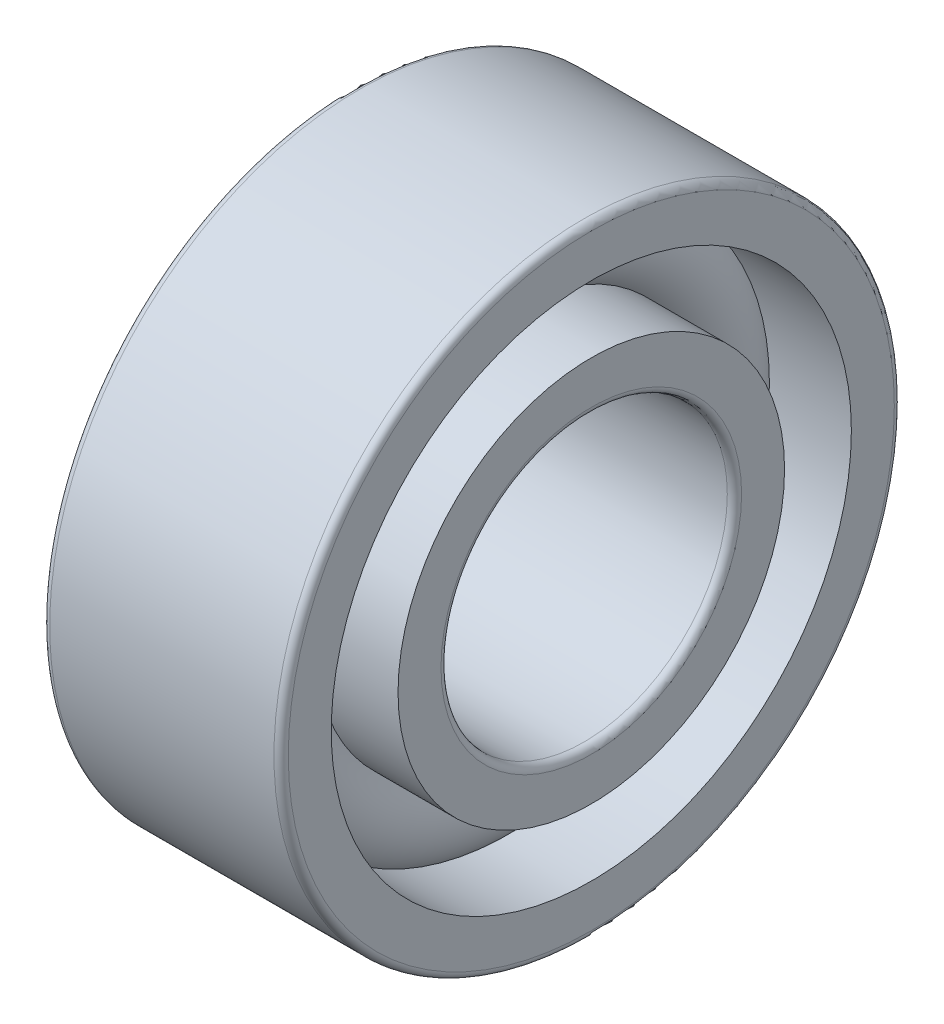
SolidWorks part; units mm, degrees
ref_plane "Plane1" through (0, 0, 0) normal (0, 0, 1) x (1, 0, 0)
ref_plane "Plane2" through (0, 0, 0) normal (0, 1, 0) x (1, 0, 0)
ref_plane "Plane3" through (0, 0, 0) normal (1, 0, 0) x (0, 0, -1)
other "Configuration Table"
sketch "Clipboard" plane through (0, 0, 0) normal (0, 0, 1) x (1, 0, 0)
  line L0 (-10, 0) -> (10, 0) construction
  line L1 (0, 0) -> (22.3471, -0.7804)
  line L2 (0, 0) -> (4.7471, 0.1658)
  line L3 (0, 0) -> (22.3471, -0.7804)
  line L4 (0, 0) -> (-22.3573, -0.3902)
  dimension "Count" = 2
sketch "CagSpiSke" plane through (0, 0, 0) normal (0, 0, 1) x (1, 0, 0)
  line L0 (0.105, 4.575) -> (0.105, 4.925)
  line L1 (0.105, 4.925) -> (-0.105, 4.925)
  line L2 (-0.105, 4.925) -> (-0.105, 4.575)
  line L3 (-0.105, 4.575) -> (0.105, 4.575)
  line L4 (-20.6375, 0) -> (20.6375, 0) construction
  line L5 (0, 0) -> (0, 23.7692) construction
revolve "CageSpine" add sketch "CagSpiSke" angle 0.001 about L4 reverse direction yes
ref_axis "Axis1" through (-50, 0, 0) along (1, 0, 0)
sketch "CagBalSke" plane through (0, 0, 0) normal (0, 0, 1) x (1, 0, 0)
  line L0 (-1.155, 4.75) -> (1.155, 4.75)
  line L1 (-1.905, 4.75) -> (1.905, 4.75) construction
  line L2 (-10, 0) -> (10, 0) construction
  line L3 (0, 0) -> (0, 24) construction
  arc A0 (1.155, 4.75) -> (-1.155, 4.75) centre (0, 4.75) cw
revolve "CageBall" [suppressed] add sketch "CagBalSke" angle 360 about L1 reverse direction yes
pattern_circular "CageBalls" [suppressed] count 2 every 180 about axis through (-50, 0, 0) along (1, 0, 0)
sketch "CagTrmODSke" plane through (0, 0, 0) normal (0, 0, 1) x (1, 0, 0)
  line L0 (1.156, 4.925) -> (1.156, 5.906)
  line L1 (1.156, 5.906) -> (-1.156, 5.906)
  line L2 (-1.156, 5.906) -> (-1.156, 4.925)
  line L3 (-1.156, 4.925) -> (1.156, 4.925)
  line L4 (-20.6375, 0) -> (20.6375, 0) construction
  line L5 (0, 0) -> (0, 25) construction
revolve "CageTrimOD" [suppressed] cut sketch "CagTrmODSke" angle 360 about L4 reverse direction yes
sketch "CagTrmIDSke" plane through (0, 0, 0) normal (0, 0, 1) x (1, 0, 0)
  line L0 (1.156, 3.596) -> (1.156, 4.575)
  line L1 (1.156, 4.575) -> (-1.156, 4.575)
  line L2 (-1.156, 4.575) -> (-1.156, 3.596)
  line L3 (-1.156, 3.596) -> (1.156, 3.596)
  line L4 (-20.6375, 0) -> (20.6375, 0) construction
  line L5 (0, 0) -> (0, 25) construction
revolve "CageTrimID" [suppressed] cut sketch "CagTrmIDSke" angle 360 about L4 reverse direction yes
sketch "BalSimSke" plane through (0, 0, 0) normal (0, 0, 1) x (1, 0, 0)
  line L0 (-10, 0) -> (10, 0) construction
  line L1 (-10, 4.75) -> (10, 4.75) construction
  line L2 (0, 0) -> (0, 23) construction
  circle A0 centre (0, 4.75) radius 1.05
revolve "BallsSimplified" add sketch "BalSimSke" angle 360 about L0
sketch "BalDetSke" plane through (0, 0, 0) normal (0, 0, 1) x (1, 0, 0)
  line L0 (-1.05, 4.75) -> (1.05, 4.75)
  line L1 (-1.905, 4.75) -> (1.905, 4.75) construction
  line L2 (0, 0) -> (0, 25) construction
  arc A0 (1.05, 4.75) -> (-1.05, 4.75) centre (0, 4.75) cw
revolve "BallDetailed" [suppressed] add sketch "BalDetSke" angle 360 about L1 reverse direction yes
sketch "InnRacSke" plane through (0, 0, 0) normal (0, 0, 1) x (1, 0, 0)
  line L0 (-0.7487, 4.05) -> (-2.5, 4.05)
  line L1 (-2.5, 4.05) -> (-2.5, 3.15)
  line L2 (-2.35, 3) -> (2.35, 3)
  line L3 (2.5, 3.15) -> (2.5, 4.05)
  line L4 (2.5, 4.05) -> (0.7487, 4.05)
  line L5 (-20.6375, 0) -> (20.6375, 0) construction
  line L6 (0, 0) -> (0, 30) construction
  arc A0 (-2.5, 3.15) -> (-2.35, 3) centre (-2.35, 3.15) ccw
  arc A1 (2.35, 3) -> (2.5, 3.15) centre (2.35, 3.15) ccw
  arc A2 (0.7487, 4.05) -> (-0.7487, 4.05) centre (0, 4.75) cw
revolve "InnerRace" add sketch "InnRacSke" angle 360 about L5 reverse direction yes
sketch "OutRacSke" plane through (0, 0, 0) normal (0, 0, 1) x (1, 0, 0)
  line L0 (-0.7487, 5.45) -> (-2.5, 5.45)
  line L1 (-2.5, 5.45) -> (-2.5, 6.35)
  line L2 (-2.35, 6.5) -> (2.35, 6.5)
  line L3 (2.5, 6.35) -> (2.5, 5.45)
  line L4 (2.5, 5.45) -> (0.7487, 5.45)
  line L5 (-20.6375, 0) -> (20.6375, 0) construction
  line L6 (0, 0) -> (0, 30) construction
  arc A0 (-2.5, 6.35) -> (-2.35, 6.5) centre (-2.35, 6.35) cw
  arc A1 (2.35, 6.5) -> (2.5, 6.35) centre (2.35, 6.35) cw
  arc A2 (0.7487, 5.45) -> (-0.7487, 5.45) centre (0, 4.75) ccw
revolve "OuterRace" add sketch "OutRacSke" angle 360 about L5 reverse direction yes
pattern_circular "BallsDetailed" [suppressed] count 2 every 180 about axis through (-50, 0, 0) along (1, 0, 0)
equation "\"BallCLRad@Clipboard\" = ( \"OD@OutRacSke\" + \"ID@InnRacSke\" ) / 4"
equation "\"BallCLRad@BalSimSke\" = \"BallCLRad@Clipboard\""
equation "\"BallCLRad@BalDetSke\" = \"BallCLRad@Clipboard\""
equation "\"BallCLRad@InnRacSke\" = \"BallCLRad@Clipboard\""
equation "\"BallCLRad@OutRacSke\" = \"BallCLRad@Clipboard\""
equation "\"Ball_diameter@InnRacSke\" = \"Ball_diameter@BalDetSke\" - 0.05"
equation "\"Ball_diameter@OutRacSke\" = \"Ball_diameter@BalDetSke\" - 0.05"
equation "\"Ball_diameter@BalSimSke\" = \"Ball_diameter@BalDetSke\""
equation "\"Width@OutRacSke\" = \"Width@InnRacSke\""
equation "\"Fillet_radius@OutRacSke\" = \"Fillet_radius@InnRacSke\""
equation "\"Max_count@Clipboard\" = int( 3.14159265 / atn(( \"Ball_diameter@BalDetSke\" / 2) / sqr( \"BallCLRad@Clipboard\"  *  \"BallCLRad@Clipboard\" - ( \"Ball_diameter@BalDetSke\" / 2) *  ( \"Ball_diameter@BalDetSke\" / 2))))"
equation "\"Max_count@Clipboard\" = ((sgn( \"Max_count@Clipboard\" - \"Count@Clipboard\" )-1)*( \"Max_count@Clipboard\" - \"Count@Clipboard\" ))/-2+ \"Count@Clipboard\""
equation "\"Count@BallsDetailed\" = int( \"Show_count@Clipboard\" ) "
equation "\"Count@BallsDetailed\" = ((sgn( \"Count@BallsDetailed\" - \"Max_count@Clipboard\" )-1)*( \"Count@BallsDetailed\" - \"Max_count@Clipboard\" ))/-2+ \"Max_count@Clipboard\""
equation "\"Count@BallsDetailed\" = ((sgn( \"Count@BallsDetailed\" - \"Min_count@Clipboard\" )+1)*( \"Count@BallsDetailed\" - \"Min_count@Clipboard\"))/2 +\"Min_count@Clipboard\""
equation "\"Angle@BallsDetailed\" = 360.0 / \"Max_count@Clipboard\""
equation "\"BallCLRad@CagBalSke\" = \"BallCLRad@Clipboard\""
equation "\"Count@CageBalls\" = \"Count@BallsDetailed\""
equation "\"Angle@CageBalls\" = \"Angle@BallsDetailed\""
equation "\"Angle@CageSpine\" =  \"Angle@CageBalls\" * ( \"Count@CageBalls\" -1 + int( \"Count@CageBalls\" / \"Max_count@Clipboard\" ) )  + 0.001 -  int( \"Count@CageBalls\" / \"Max_count@Clipboard\" ) * 0.001"
equation "\"Angle@CageSpine\" =  \"Angle@CageSpine\" * int( \"Min_count@Clipboard\" / 2) + int(1 / \"Min_count@Clipboard\")  * 0.001"
equation "\"CageWallOD@CagBalSke\" =  \"Ball_diameter@BalDetSke\" * 1.1"
equation "\"Thickness@CagSpiSke\" =  \"Ball_diameter@BalDetSke\" * 0.1"
equation "\"OD@CagTrmODSke\" = \"BallCLRad@Clipboard\" * 2 + \"CageWallOD@CagBalSke\" + 0.002"
equation "\"ID@CagTrmODSke\" = \"BallCLRad@Clipboard\" * 2 + \"Ball_diameter@BalDetSke\" / 6"
equation "\"OD@CagTrmIDSke\" = \"BallCLRad@Clipboard\" * 2 - \"Ball_diameter@BalDetSke\" / 6"
equation "\"ID@CagTrmIDSke\" = \"BallCLRad@Clipboard\" * 2 - \"CageWallOD@CagBalSke\" + 0.002"
equation "\"OD@CagSpiSke\" = \"ID@CagTrmODSke\""
equation "\"ID@CagSpiSke\" = \"OD@CagTrmIDSke\""
equation "\"Width@CagTrmODSke\" = \"CageWallOD@CagBalSke\" + 0.002"
equation "\"Width@CagTrmIDSke\" = \"CageWallOD@CagBalSke\" + 0.002"
